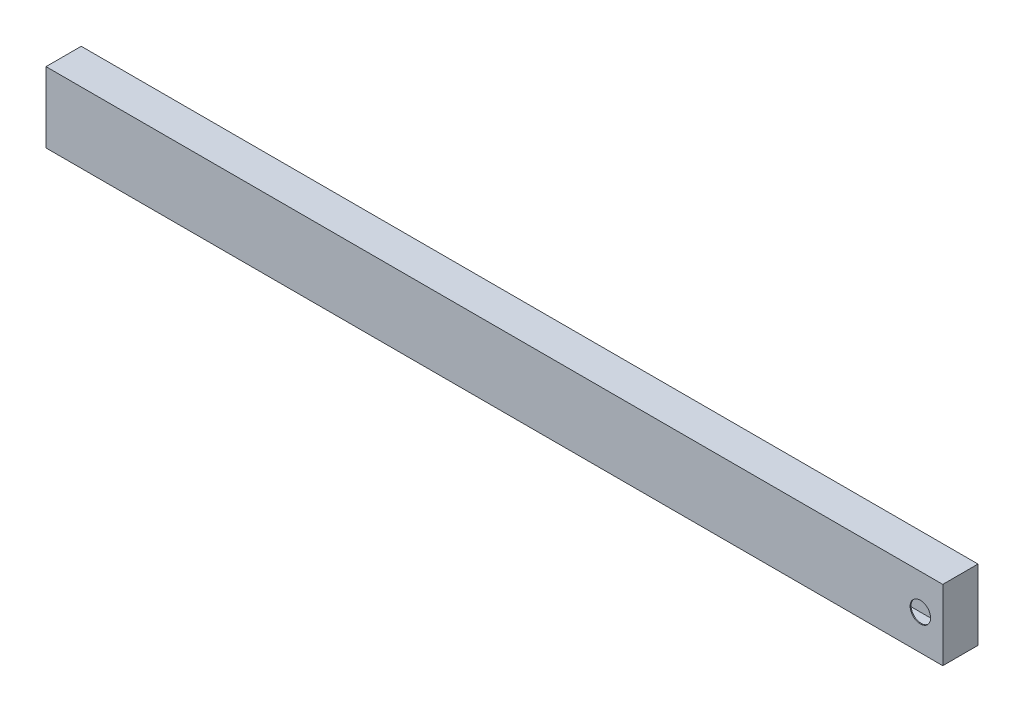
SolidWorks part; units mm, degrees
ref_plane "Спереди" through (0, 0, 0) normal (0, 0, 1) x (1, 0, 0)
ref_plane "Сверху" through (0, 0, 0) normal (0, 1, 0) x (1, 0, 0)
ref_plane "Справа" through (0, 0, 0) normal (1, 0, 0) x (0, 0, -1)
sketch "Эскиз1" plane through (0, 0, 0) normal (0, 1, 0) x (1, 0, 0)
  line L1 (0, 0) -> (-1400, 0)
  line L2 (0, 0) -> (0, 55)
  line L3 (0, 55) -> (-1400, 55)
  line L4 (-1400, 0) -> (-1400, 55)
  dimension "D1" = 1400
  dimension "D2" = 55
extrude "Бобышка-Вытянуть1" add sketch "Эскиз1" along normal blind 110
sketch "Эскиз2" plane through (0, 0, 0) normal (1, 0, 0) x (0, 0, -1)
  line L0 (55, 110) -> (55, 0) construction
  line L1 (53.5, 108.5) -> (1.5, 108.5)
  line L2 (53.5, 108.5) -> (53.5, 1.5)
  line L3 (53.5, 1.5) -> (1.5, 1.5)
  line L4 (1.5, 108.5) -> (1.5, 1.5)
  line L5 (0, 110) -> (55, 110) construction
  point P4 (53.5, 55)
  point P7 (55, 55)
  point P8 (27.5, 108.5)
  point P11 (27.5, 110)
  dimension "D1" = 107
  dimension "D2" = 52
sketch "Эскиз3" plane through (0, 0, -55) normal (0, 0, -1) x (-1, 0, 0)
  line L0 (0, 110) -> (0, 0) construction
  line L2 (1400, 110) -> (1400, 0) construction
  circle A0 centre (70, 55) radius 30
  circle A1 centre (175, 55) radius 30
  circle A2 centre (280, 55) radius 30
  circle A3 centre (385, 55) radius 30
  circle A4 centre (490, 55) radius 30
  circle A5 centre (595, 55) radius 30
  circle A6 centre (700, 55) radius 30
  circle A7 centre (805, 55) radius 30
  circle A8 centre (910, 55) radius 30
  circle A10 centre (1380, 55) radius 2.5
  circle A11 centre (1015, 55) radius 30
  circle A12 centre (1120, 55) radius 30
  circle A13 centre (1225, 55) radius 30
  circle A15 centre (1330, 55) radius 30
  point P5 (0, 55)
  dimension "D1" = 60
  dimension "D5" = 5
  dimension "D6" = 20
  dimension "D2" = 70
  dimension "D4" = 105
  dimension "D3" = 13
extrude "Вырез-Вытянуть1" cut sketch "Эскиз3" against normal blind 10
sketch "Эскиз4" plane through (0, 0, 0) normal (1, 0, 0) x (0, 0, -1)
  line L0 (55, 110) -> (55, 0) construction
  line L1 (53.5, 108.5) -> (1.5, 108.5)
  line L2 (53.5, 108.5) -> (53.5, 1.5)
  line L3 (53.5, 1.5) -> (1.5, 1.5)
  line L4 (1.5, 108.5) -> (1.5, 1.5)
  line L5 (0, 110) -> (55, 110) construction
  dimension "D1" = 107
  dimension "D2" = 52
  dimension "D3" = 1.5
  dimension "D4" = 1.5
extrude "Вырез-Вытянуть2" cut sketch "Эскиз4" against normal blind 1394 from offset 3 offset against normal yes
sketch "Эскиз5" plane through (0, 0, 0) normal (0, 0, 1) x (1, 0, 0)
  line L0 (-1400, 110) -> (-1400, 0) construction
  line L1 (0, 108.5) -> (0, 1.5) construction
  circle A0 centre (-35, 55) radius 16
  point P5 (-1400, 55)
  dimension "D1" = 32
  dimension "D2" = 35
extrude "Вырез-Вытянуть3" cut sketch "Эскиз5" against normal blind 10
